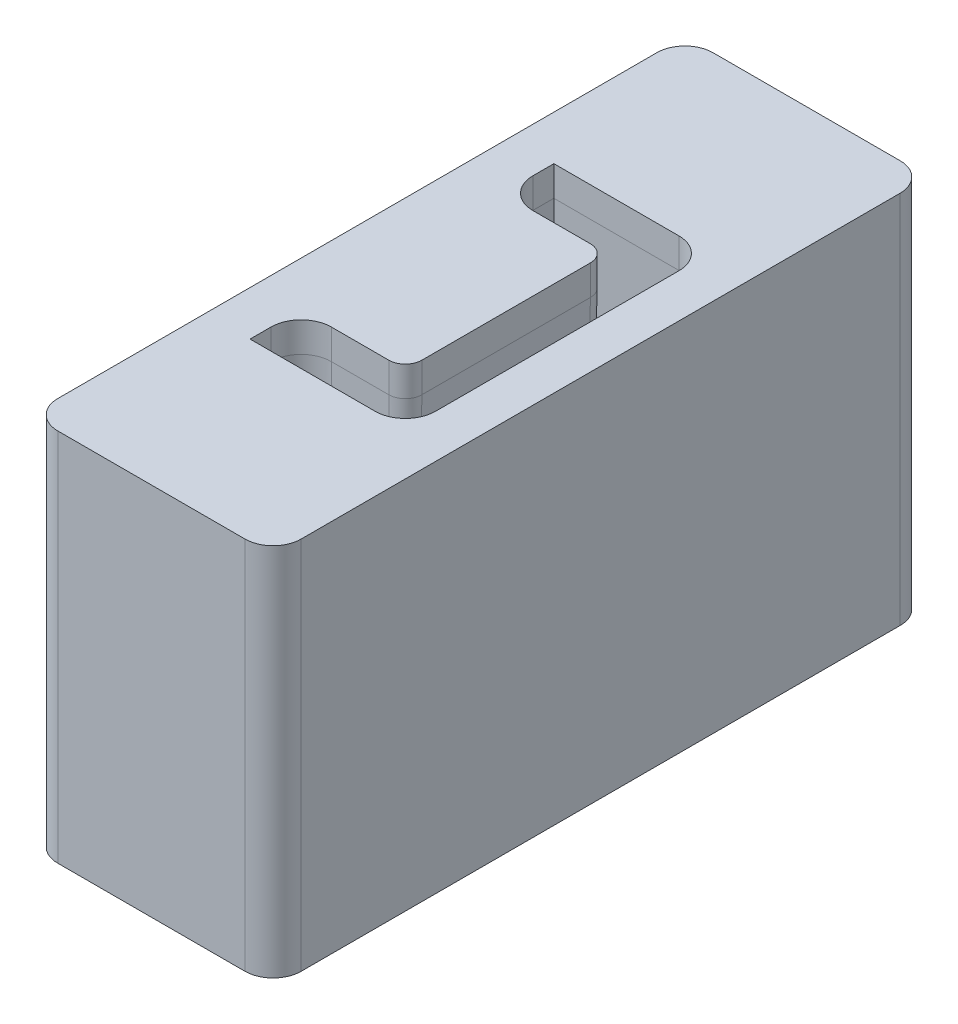
SolidWorks part; units mm, degrees
material "K110"
ref_plane "Front Plane" through (0, 0, 0) normal (0, 0, 1) x (1, 0, 0)
ref_plane "Top Plane" through (0, 0, 0) normal (0, 1, 0) x (1, 0, 0)
ref_plane "Right Plane" through (0, 0, 0) normal (1, 0, 0) x (0, 0, -1)
sketch "Sketch1" plane through (0, 0, 0) normal (0, 1, 0) x (1, 0, 0)
  line L1 (-13, -35) -> (13, -35)
  line L2 (-13, -35) -> (-13, 35)
  line L3 (-13, 35) -> (13, 35)
  line L4 (13, -35) -> (13, 35)
  line L5 (-13, -35) -> (13, 35) construction
  line L6 (-13, 35) -> (13, -35) construction
  point P0 (0, 0)
  dimension "D1" = 70
  dimension "D2" = 26
extrude "Boss-Extrude1" add sketch "Sketch1" against normal blind 40
fillet "Fillet1" radius 3 4 edges at (-13, -20, -35) (13, -20, -35) (-13, -20, 35) (13, -20, 35)
sketch "Sketch9" plane through (0, 0, 0) normal (0, 1, 0) x (1, 0, 0)
  line L72 (2.9, 9) -> (2.9, -9)
  line L73 (1.13, -10.77) -> (-5, -10.77)
  line L74 (-8.23, -14) -> (-8.23, -16.23)
  line L75 (-8.23, -16.23) -> (5.13, -16.23)
  line L76 (8.36, -13) -> (8.36, 13)
  line L77 (5.13, 16.23) -> (-8.23, 16.23)
  line L78 (-8.23, 16.23) -> (-8.23, 14)
  line L79 (-5, 10.77) -> (1.13, 10.77)
  line L80 (2.9, 9) -> (2.9, -9)
  line L81 (1.13, -10.77) -> (-5, -10.77)
  line L82 (-8.23, -14) -> (-8.23, -16.23)
  line L83 (-8.23, -16.23) -> (5.13, -16.23)
  line L84 (8.36, -13) -> (8.36, 13)
  line L85 (5.13, 16.23) -> (-8.23, 16.23)
  line L86 (-8.23, 16.23) -> (-8.23, 14)
  line L87 (-5, 10.77) -> (1.13, 10.77)
  arc A54 (2.9, 9) -> (1.13, 10.77) centre (1.13, 9) ccw
  arc A55 (1.13, -10.77) -> (2.9, -9) centre (1.13, -9) ccw
  arc A56 (-5, -10.77) -> (-8.23, -14) centre (-5, -14) ccw
  arc A57 (5.13, -16.23) -> (8.36, -13) centre (5.13, -13) ccw
  arc A58 (8.36, 13) -> (5.13, 16.23) centre (5.13, 13) ccw
  arc A59 (-8.23, 14) -> (-5, 10.77) centre (-5, 14) ccw
  arc A60 (2.9, 9) -> (1.13, 10.77) centre (1.13, 9) ccw
  arc A61 (1.13, -10.77) -> (2.9, -9) centre (1.13, -9) ccw
  arc A62 (-5, -10.77) -> (-8.23, -14) centre (-5, -14) ccw
  arc A63 (5.13, -16.23) -> (8.36, -13) centre (5.13, -13) ccw
  arc A64 (8.36, 13) -> (5.13, 16.23) centre (5.13, 13) ccw
  arc A65 (-8.23, 14) -> (-5, 10.77) centre (-5, 14) ccw
  dimension "D1" = 0.23
extrude "Cut-Extrude1" cut sketch "Sketch9" against normal up to next
sketch "Sketch11" plane through (0, 0, 0) normal (0, 0, 1) x (1, 0, 0)
  line L0 (8.36, -3.2) -> (9.0023, -40)
  line L2 (-10, -40) -> (10, -40) construction
  line L3 (9.0023, -40) -> (8.36, -40)
  line L4 (8.36, -40) -> (8.36, -3.2)
  line L5 (14.3, 0) -> (-14.3, 0) construction
  line L6 (8.36, -40) -> (8.36, 0) construction
  point P2 (0, 0)
  point P11 (0, 0)
  dimension "D1" = 3.2
  dimension "D2" = 1
sketch "Sketch12" plane through (0, 0, 0) normal (0, 1, 0) x (1, 0, 0)
  line L16 (-8.23, -14) -> (-8.23, -16.23) construction
  line L17 (1.13, -10.77) -> (-5, -10.77) construction
  line L18 (-8.23, 16.23) -> (-8.23, 14) construction
  line L19 (-5, 10.77) -> (1.13, 10.77) construction
  line L20 (2.9, 9) -> (2.9, -9) construction
  line L21 (-8.23, -16.23) -> (5.13, -16.23) construction
  line L22 (8.36, -13) -> (8.36, 13) construction
  line L23 (5.13, 16.23) -> (-8.23, 16.23) construction
  line L24 (-8.23, -14) -> (-8.23, -16.23)
  line L25 (1.13, -10.77) -> (-5, -10.77)
  line L26 (-8.23, 16.23) -> (-8.23, 14)
  line L27 (-5, 10.77) -> (1.13, 10.77)
  line L28 (2.9, 9) -> (2.9, -9)
  line L29 (-8.23, -16.23) -> (5.13, -16.23)
  line L30 (8.36, -13) -> (8.36, 13)
  line L31 (5.13, 16.23) -> (-8.23, 16.23)
  arc A12 (-5, -10.77) -> (-8.23, -14) centre (-5, -14) ccw construction
  arc A13 (1.13, -10.77) -> (2.9, -9) centre (1.13, -9) ccw construction
  arc A14 (-8.23, 14) -> (-5, 10.77) centre (-5, 14) ccw construction
  arc A15 (2.9, 9) -> (1.13, 10.77) centre (1.13, 9) ccw construction
  arc A16 (5.13, -16.23) -> (8.36, -13) centre (5.13, -13) ccw construction
  arc A17 (8.36, 13) -> (5.13, 16.23) centre (5.13, 13) ccw construction
  arc A18 (-5, -10.77) -> (-8.23, -14) centre (-5, -14) ccw
  arc A19 (1.13, -10.77) -> (2.9, -9) centre (1.13, -9) ccw
  arc A20 (-8.23, 14) -> (-5, 10.77) centre (-5, 14) ccw
  arc A21 (2.9, 9) -> (1.13, 10.77) centre (1.13, 9) ccw
  arc A22 (5.13, -16.23) -> (8.36, -13) centre (5.13, -13) ccw
  arc A23 (8.36, 13) -> (5.13, 16.23) centre (5.13, 13) ccw
sweep "Cut-Sweep1" cut profiles "Sketch11" path "Sketch12"
hole_wizard "M8 Tapped Hole1" positions "Sketch16" profile "Sketch14" tap size "M8" standard "ISO"
sketch "Sketch16" plane through (0, -40, 0) normal (0, -1, 0) x (-1, 0, 0)
  line L0 (0, 22) -> (0, -22) construction
  line L2 (0, -35) -> (0, -16.8723) construction
  line L3 (10, -35) -> (-10, -35) construction
  line L5 (0, 35) -> (0, 16.8723) construction
  line L6 (-10, 35) -> (10, 35) construction
  line L10 (8.8723, 16.8723) -> (-5.13, 16.8723) construction
  line L11 (-5.13, -16.8723) -> (8.8723, -16.8723) construction
  point P0 (0, -25.9362)
  point P4 (0, 25.9362)
  point P30 (0, 0)
  point P33 (0, 0)
  point P36 (0, 0)
  point P37 (0, 0)
sketch "Sketch14" plane through (0, -40, 25.9362) normal (1, 0, 0) x (0, 0, -1)
  line L0 (0, 0) -> (0, 24.2929)
  line L1 (0, 24.2929) -> (3.4, 22.25)
  line L2 (3.4, 22.25) -> (3.4, 0)
  line L5 (3.4, 0) -> (0, 0)
  line L10 (0, 24.2929) -> (-3.4, 22.25) construction
  line L11 (0, -6.35) -> (0, 107.95) construction
  dimension "Tap Drill Dia." = 6.8
  dimension "Tap Drill Depth" = 22.25
  dimension "Drill Angle" = 118
cosmetic thread "Hole Thread7"
cosmetic thread "Hole Thread8"
